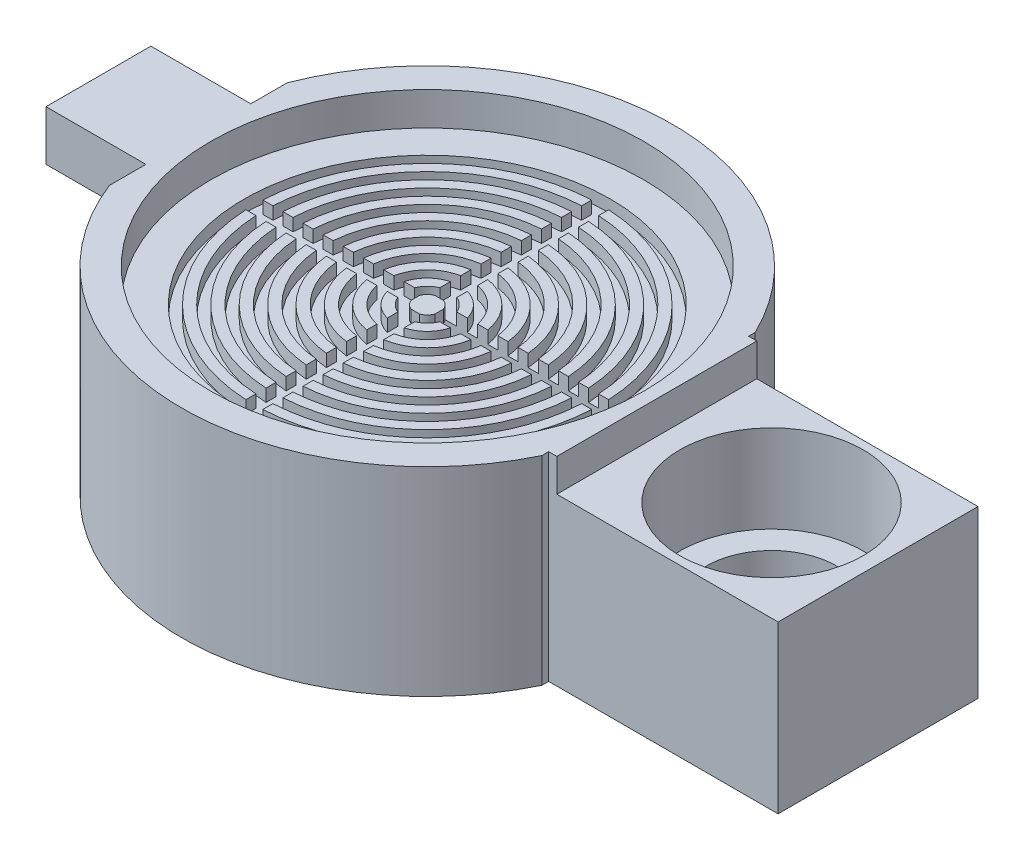
SolidWorks part; units mm, degrees
ref_plane "Front Plane" through (0, 0, 0) normal (0, 0, 1) x (1, 0, 0)
ref_plane "Top Plane" through (0, 0, 0) normal (0, 1, 0) x (1, 0, 0)
ref_plane "Right Plane" through (0, 0, 0) normal (1, 0, 0) x (0, 0, -1)
ref_axis "Axis1" through (0, 6.1341, 0) along (0, -1, 0)
sketch "Sketch1" plane through (0, 0, 0) normal (0, 1, 0) x (1, 0, 0)
  circle A0 centre (0, 0) radius 14.986
  dimension "D1" = 29.972
extrude "Circular Membrane Holder" add sketch "Sketch1" along normal blind 5.842 and the other way blind 6.3
sketch "Sketch11" plane through (0, -6.3, 0) normal (0, -1, 0) x (1, 0, 0)
  circle A0 centre (0, 0) radius 10.922
  circle A1 centre (0, 0) radius 8.89
  dimension "D1" = 21.844
  dimension "D2" = 17.78
extrude "Stabilizer - Undermount" add sketch "Sketch11" along normal blind 1.016
sketch "Sketch2" plane through (0, 5.842, 0) normal (0, 1, 0) x (1, 0, 0)
  circle A0 centre (0, 0) radius 13.208
  dimension "D1" = 26.416
extrude "Membrane Well" cut sketch "Sketch2" against normal blind 2.032
sketch "Sketch3" plane through (0, 3.81, 0) normal (0, 1, 0) x (1, 0, 0)
  circle A0 centre (0, 0) radius 11.176
  circle A2 centre (0, 0) radius 13.208 construction
  dimension "D1" = 2.032
extrude "Permeate Collection Well" cut sketch "Sketch3" against normal blind 0.762
sketch "Sketch4" plane through (0, 3.048, 0) normal (0, 1, 0) x (1, 0, 0)
  circle A1 centre (0, 0) radius 1.9939
  circle A7 centre (0, 0) radius 10.5639
  circle A8 centre (0, 0) radius 9.9517
  circle A9 centre (0, 0) radius 9.3396
  circle A10 centre (0, 0) radius 8.7274
  circle A11 centre (0, 0) radius 8.1153
  circle A12 centre (0, 0) radius 7.5032
  circle A20 centre (0, 0) radius 11.176 construction
  circle A21 centre (0, 0) radius 6.891
  circle A22 centre (0, 0) radius 6.2789
  circle A23 centre (0, 0) radius 5.6667
  circle A24 centre (0, 0) radius 5.0546
  circle A25 centre (0, 0) radius 4.4425
  circle A26 centre (0, 0) radius 3.8303
  circle A27 centre (0, 0) radius 3.2182
  circle A28 centre (0, 0) radius 2.606
  circle A29 centre (0, 0) radius 1.3818
  circle A30 centre (0, 0) radius 0.7696
  dimension "D1" = 0.6121
  dimension "D2" = 0.6121
  dimension "D3" = 0.6121
  dimension "D4" = 0.6121
  dimension "D5" = 0.6121
  dimension "D6" = 0.6121
  dimension "D7" = 0.6121
  dimension "D8" = 0.6121
  dimension "D9" = 0.6121
  dimension "D10" = 0.6121
  dimension "D11" = 0.6121
  dimension "D12" = 0.6121
  dimension "D13" = 0.6121
  dimension "D14" = 0.6121
  dimension "D15" = 0.6121
  dimension "D16" = 0.6121
  dimension "D17" = 0.6121
  dimension "D18" = 1.5392
extrude "Membrane Support - Permeate Well" add sketch "Sketch4" along normal up to surface (0.762 mm away) contours A7 A8 | A9 A10 | A11 A12 | A21 A22 | A23 A24 | A25 A26 | A27 A28 | A1 A29 | A30 region at (-1.9375, 3.048, 0) region at (-10.2651, 3.048, 0) region at (-9.0754, 3.048, 0) region at (-7.8858, 3.048, 0) region at (-6.6961, 3.048, 0) region at (-5.5065, 3.048, 0) region at (-4.3168, 3.048, 0) region at (-3.1272, 3.048, 0) region at (0, 3.048, 0) up to face at (0, 3.81, 11.176)
sketch "Sketch5" plane through (0, 3.81, 0) normal (0, 1, 0) x (1, 0, 0)
  line L1 (-0.5156, 0.7241) -> (0.5156, 0.7241)
  line L2 (-0.5156, 0.7241) -> (-0.5156, 10.6927)
  line L3 (-0.5156, 10.6927) -> (0.5156, 10.6927)
  line L4 (0.5156, 0.7241) -> (0.5156, 10.6927)
extrude "Permeate Well Branches" cut sketch "Sketch5" against normal up to surface (0.762 mm away) up to face at (0, 3.048, 10.5639)
pattern_circular "CirPattern1" count 4 over 360 about axis through (0, 6.1341, 0) along (0, -1, 0) of "Permeate Well Branches"
sketch "Sketch6" plane through (0, 3.048, 0) normal (0, 1, 0) x (1, 0, 0)
  line L0 (0, 0.5156) -> (0.5156, 0.5156)
  line L1 (11.1641, 0.5156) -> (0.5156, 0.5156)
  line L2 (11.1641, 0.5156) -> (11.1641, -0.5156)
  line L3 (11.1641, -0.5156) -> (0.5156, -0.5156)
  line L5 (0, -0.5156) -> (0.5156, -0.5156)
  circle A0 centre (0, 0) radius 11.176 construction
  arc A1 (0, -0.5156) -> (0, 0.5156) centre (0, 0) ccw
extrude "Well to Outlet" cut sketch "Sketch6" against normal blind 1.016
sketch "Sketch7" plane through (0, -6.3, 0) normal (0, -1, 0) x (1, 0, 0)
  line L2 (-13.97, 25.4) -> (-13.97, -25.4)
  line L4 (13.5, 25.4) -> (13.5, -25.4)
  line L5 (-13.97, 25.4) -> (-17.9267, 25.4)
  line L6 (-13.97, 25.4) -> (-13.97, -25.4)
  line L7 (-13.97, -25.4) -> (-17.9267, -25.4)
  line L8 (-17.9267, 25.4) -> (-17.9267, -25.4)
  line L9 (13.5, -25.4) -> (17.8379, -25.4)
  line L10 (13.5, -25.4) -> (13.5, 25.4)
  line L11 (13.5, 25.4) -> (17.8379, 25.4)
  line L12 (17.8379, -25.4) -> (17.8379, 25.4)
  circle A0 centre (0, 0) radius 14.986 construction
  circle M5 centre (0, 0) radius 14.986
  dimension "D1" = 13.97
  dimension "D2" = 13.5
extrude "Flatten Round Edges" cut sketch "Sketch7" against normal through all contours L5 L8 L7 L2 M5 | L9 L12 L11 L4 M5 | L2 M5 | L4 M5 region at (-16.0084, -6.3, 0) region at (-14.3776, -6.3, 0) region at (14.097, -6.3, 0) region at (15.7677, -6.3, 0)
sketch "Sketch8" plane through (-13.97, 0, 0) normal (-1, 0, 0) x (0, 0, 1)
  line L0 (5.424, 5.842) -> (-5.424, 5.842) construction
  line L1 (-3.2, 5.842) -> (3.2, 5.842)
  line L2 (-3.2, 5.842) -> (-3.2, 2.794)
  line L3 (-3.2, 2.794) -> (3.2, 2.794)
  line L4 (3.2, 5.842) -> (3.2, 2.794)
  line L5 (0, -6.9674) -> (0, 6.9674) construction
  dimension "D1" = 3.2
  dimension "D2" = 3.2
  dimension "D3" = 3.048
extrude "Stabilizer - Non Permeate" add sketch "Sketch8" along normal blind 6.096
sketch "Sketch22" plane through (13.5, 0, 0) normal (1, 0, 0) x (0, 0, -1)
  line L0 (6.5062, -6.3) -> (6.5062, 5.842) construction
  line L1 (-6.0938, 5.842) -> (6.1062, 5.842)
  line L2 (-6.0938, 5.842) -> (-6.0938, -6.3)
  line L3 (-6.0938, -6.3) -> (6.1062, -6.3)
  line L4 (6.1062, 5.842) -> (6.1062, -6.3)
  line L5 (-6.5062, 5.842) -> (-6.5062, -6.3) construction
  line L6 (6.5062, 5.842) -> (-6.5062, 5.842) construction
  line L8 (-10.922, -6.3) -> (10.922, -6.3) construction
  dimension "D1" = 0
  dimension "D2" = 0.4
  dimension "D4" = 0.4123
extrude "Stabilizer - Permeate Side" add sketch "Sketch22" along normal blind 14
ref_plane "Plane3" through (21, 0, 0) normal (1, 0, 0) x (0, 0, -1)
sketch "Sketch14" plane through (0, 2.032, 0) normal (0, 1, 0) x (1, 0, 0)
  line L0 (11.1641, 0.5156) -> (0, 0.5156) construction
  line L1 (11.1641, -0.5156) -> (9.5128, -0.5156)
  line L2 (11.1641, -0.5156) -> (11.1641, 0.5156)
  line L3 (11.1641, 0.5156) -> (9.5128, 0.5156)
  arc A0 (9.5128, 0.5156) -> (9.5128, -0.5156) centre (9.5128, 0) ccw
extrude "Cut-Extrude8" cut sketch "Sketch14" against normal blind 0.762
sketch "Sketch18" plane through (0, 0, 0) normal (0, 0, 1) x (1, 0, 0)
  line L0 (10.6561, 1.7272) -> (13.6561, -2.6728)
  line L1 (13.6561, -2.6728) -> (23.6561, -2.6728)
  line L5 (11.1641, 1.27) -> (9.5128, 1.27) construction
  dimension "D1" = 3
  dimension "D3" = 0.4572
  dimension "D4" = 4.4
  dimension "D7" = 10
sketch "Sketch41" plane through (0, 0, -6.1062) normal (0, 0, -1) x (-1, 0, 0)
  line L0 (-26, -3.6) -> (-26, -6.3)
  line L1 (-26, -6.3) -> (-16, -6.3)
  line L2 (-16, -6.3) -> (-16, -3.6)
  line L3 (-16, -3.6) -> (-26, -3.6)
  line L4 (-27.5, -6.3) -> (-27.5, 5.842) construction
  line L5 (-27.5, -6.3) -> (-13.5, -6.3) construction
  dimension "D1" = 1.5
  dimension "D2" = 0
  dimension "D3" = 2.7
extrude "Probe Slit Cut Out" cut sketch "Sketch41" against normal blind 9.5
sketch "Sketch34" plane through (0, 0, -6.1062) normal (0, 0, -1) x (-1, 0, 0)
  line L0 (-26, -6.3) -> (-26, -3.6)
  line L1 (-26, -6.3) -> (-16, -6.3) construction
  line L3 (-26, -3.6) -> (-24.9, -3.6)
  line L4 (-24.9, -3.6) -> (-24.9, -4.5)
  line L5 (-24.9, -4.5) -> (-17.1, -4.5)
  line L6 (-17.1, -4.5) -> (-17.1, -3.6)
  line L7 (-17.1, -3.6) -> (-16, -3.6)
  line L8 (-27.5, -6.3) -> (-27.5, 5.842) construction
  line L9 (-16, -3.6) -> (-16, -6.3)
  line L10 (-16, -6.3) -> (-26, -6.3)
  dimension "D1" = 1.5
  dimension "D2" = 0
  dimension "D3" = 2.7
extrude "Probe Slit Insert" add sketch "Sketch34" against normal blind 11
sketch "Sketch48" plane through (0, 5.842, 0) normal (0, 1, 0) x (1, 0, 0)
  line L1 (27.5, 6.1062) -> (27.5, -6.0938) construction
  line L2 (27.5, 6.1062) -> (13.5, 6.1062) construction
  line L3 (27.5, -6.0938) -> (13.5, -6.0938) construction
  circle A0 centre (21, 0.0062) radius 5.6
  dimension "D1" = 6.5
  dimension "D2" = 6.1
  dimension "D3" = 6.1
ref_axis "Axis2" through (13.6561, -2.6728, 0) along (1, 0, 0)
extrude "Stir Bar Area" cut sketch "Sketch48" against normal blind 7.35
sketch "Sketch42" plane through (0, 5.842, 0) normal (0, 1, 0) x (1, 0, 0)
  line L0 (27.5, 6.1062) -> (27.5, -6.0938) construction
  line L1 (27.5, 6.1062) -> (13.5, 6.1062) construction
  line L2 (27.5, -6.0938) -> (13.5, -6.0938) construction
  circle A0 centre (21, 0.0062) radius 4
  dimension "D1" = 6.5
  dimension "D2" = 6.1
  dimension "D3" = 6.1
extrude "Probe Area " cut sketch "Sketch42" against normal up to surface (9.442 mm away) up to face at (21, -3.6, -1.3562)
sketch "Sketch47" plane through (21, 0, 0) normal (1, 0, 0) x (0, 0, -1)
  circle A0 centre (0, -2.6728) radius 0.6
sweep "Cut-Sweep1" cut profiles "Sketch47" path "Sketch18"
sketch "Sketch50" plane through (0, 5.842, 0) normal (0, 1, 0) x (1, 0, 0)
  line L0 (27.5, 6.1062) -> (14, 6.1062)
  line L1 (27.5, 6.1062) -> (13.5, 6.1062) construction
  line L2 (14, 6.1062) -> (14, -6.0938)
  line L3 (27.5, -6.0938) -> (13.5, -6.0938) construction
  line L4 (14, -6.0938) -> (27.5, -6.0938)
  line L5 (27.5, -6.0938) -> (27.5, 6.1062)
  circle A1 centre (21, 0.0062) radius 5.6 construction
  dimension "D1" = 6.1
  dimension "D2" = 6.1
  dimension "D3" = 6.5
  dimension "D4" = 7
extrude "Cut-Extrude9" cut sketch "Sketch50" against normal blind 2
sketch "Sketch52" plane through (0, 0, -6.1062) normal (0, 0, -1) x (-1, 0, 0)
